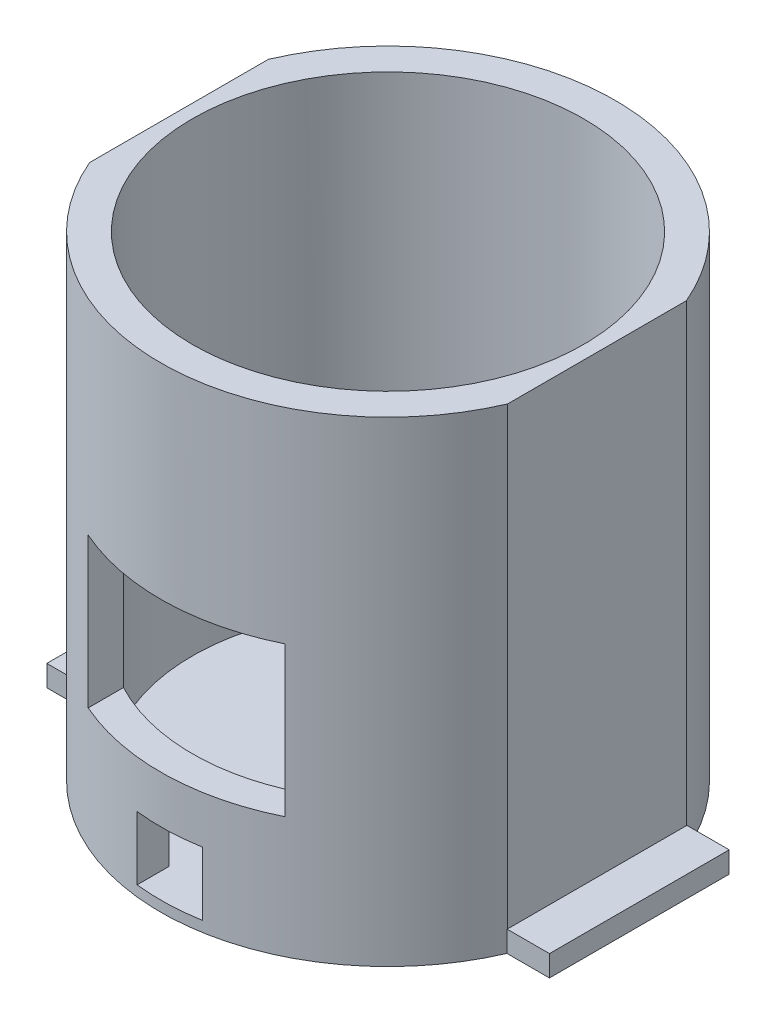
SolidWorks part; units mm, degrees
ref_plane "Front Plane" through (0, 0, 0) normal (0, 0, 1) x (1, 0, 0)
ref_plane "Top Plane" through (0, 0, 0) normal (0, 1, 0) x (1, 0, 0)
ref_plane "Right Plane" through (0, 0, 0) normal (1, 0, 0) x (0, 0, -1)
sketch "Sketch1" plane through (0, 0, 0) normal (0, 1, 0) x (1, 0, 0)
  line L0 (-19.769, 8.4519) -> (-19.769, -8.4519)
  line L1 (19.769, 8.4519) -> (19.769, -8.4519)
  line L2 (0, 0) -> (21.5, 0) construction
  circle A0 centre (0, 0) radius 18.5
  circle A1 centre (0, 0) radius 21.5
  point P9 (19.769, 0)
  dimension "D1" = 37
  dimension "D2" = 3
extrude "Boss-Extrude1" add sketch "Sketch1" along normal blind 45 contours A0 L1 A1 L0 region at (0, 0, -20.9159)
extrude "Boss-Extrude2" add sketch "Sketch1<3>" along normal blind 1 contours A0 region at (0, 0, 0)
sketch "Sketch1<3>" plane through (0, 0, 0) normal (0, 1, 0) x (1, 0, 0) same geometry as "Sketch1"
sketch "Sketch2" plane through (0, 0, 0) normal (0, 0, 1) x (1, 0, 0)
  line L0 (18.5, 1) -> (-18.5, 1) construction
  line L1 (-2.3594, 1) -> (3.6406, 1)
  line L2 (-2.3594, 1) -> (-2.3594, 7)
  line L3 (-2.3594, 7) -> (3.6406, 7)
  line L4 (3.6406, 1) -> (3.6406, 7)
  line L5 (-8.6857, 25.6342) -> (9.5256, 25.6342)
  line L6 (-8.6857, 25.6342) -> (-8.6857, 11.4782)
  line L7 (-8.6857, 11.4782) -> (9.5256, 11.4782)
  line L8 (9.5256, 25.6342) -> (9.5256, 11.4782)
  point P10 (0, 0)
  point P11 (9.5256, 24.2822)
  dimension "D1" = 6
  dimension "D2" = 6
extrude "Cut-Extrude1" cut sketch "Sketch2" along normal up to surface (21.3702 mm away) up to face at (0, 22.5, 14.976)
sketch "Sketch3" plane through (0, 0, 0) normal (0, 0, 1) x (1, 0, 0)
  line L0 (-19.769, 45) -> (-19.769, 0) construction
  line L1 (-19.769, 0) -> (-23.769, 0)
  line L2 (-19.769, 0) -> (-19.769, 2)
  line L3 (-19.769, 2) -> (-23.769, 2)
  line L4 (-23.769, 0) -> (-23.769, 2)
  dimension "D1" = 2
  dimension "D2" = 4
extrude "Boss-Extrude3" add sketch "Sketch3" along normal mid plane 17
mirror "Mirror1" about plane through (0, 0, 0) normal (1, 0, 0) of "Boss-Extrude3"
